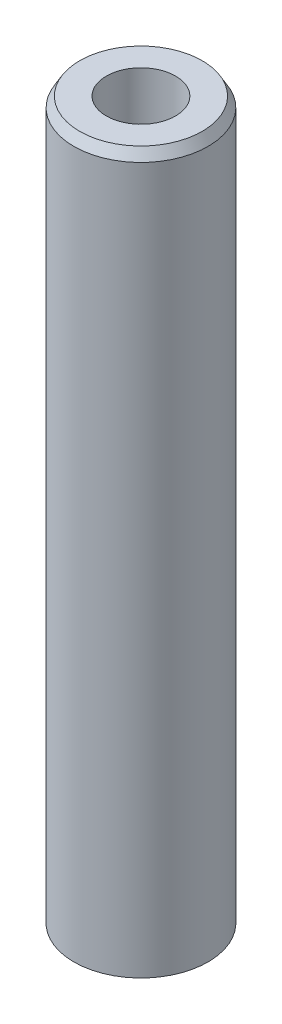
SolidWorks part; units mm, degrees
ref_plane "Front Plane" through (0, 0, 0) normal (0, 0, 1) x (1, 0, 0)
ref_plane "Top Plane" through (0, 0, 0) normal (0, 1, 0) x (1, 0, 0)
ref_plane "Right Plane" through (0, 0, 0) normal (1, 0, 0) x (0, 0, -1)
sketch "Sketch1" plane through (0, 0, 0) normal (0, 1, 0) x (1, 0, 0)
  circle A0 centre (0, 0) radius 17.5
  dimension "SHAFT_OD" = 35
extrude "Boss-Extrude1" add sketch "Sketch1" along normal blind 188.3552
sketch "Sketch2" plane through (0, 0, 0) normal (0, 1, 0) x (1, 0, 0)
  circle A0 centre (0, 0) radius 9.0276
  dimension "BORE_D" = 18.0553
extrude "Cut-Extrude1" cut sketch "Sketch2" along normal through all
chamfer "Chamfer1" distance 2.6376 angle 30 2 edges at (0, 188.3552, 17.5) (0, 0, 17.5) first distance on face at (0, 188.3552, 17.5) first distance on face at (0, 0, 9.0276)
